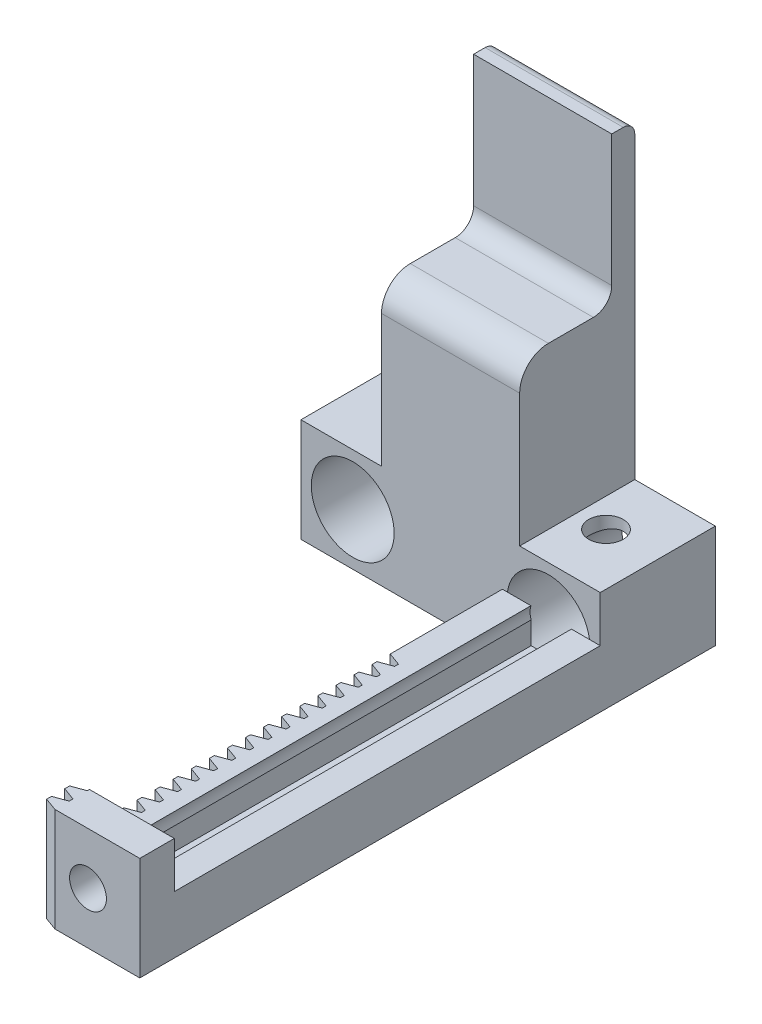
SolidWorks part; units mm, degrees
ref_plane "前视基准面" through (0, 0, 0) normal (0, 0, 1) x (1, 0, 0)
ref_plane "上视基准面" through (0, 0, 0) normal (0, 1, 0) x (1, 0, 0)
ref_plane "右视基准面" through (0, 0, 0) normal (1, 0, 0) x (0, 0, -1)
other "Configuration Table"
sketch "草图1" plane through (0, 0, 0) normal (0, 0, 1) x (1, 0, 0)
  line L1 (-13, 4.5) -> (13, 4.5)
  line L2 (-13, 4.5) -> (-13, -4.5)
  line L3 (-13, -4.5) -> (13, -4.5)
  line L4 (13, 4.5) -> (13, -4.5)
  line L5 (-13, 4.5) -> (13, -4.5) construction
  line L6 (-13, -4.5) -> (13, 4.5) construction
  point P0 (0, 0)
  dimension "D1" = 26
  dimension "D2" = 9
extrude "凸台-拉伸1" add sketch "草图1" against normal blind 10
sketch "草图2" plane through (0, 0, 0) normal (0, 0, 1) x (1, 0, 0)
  line L0 (0, 8.6502) -> (0, -9.0329) construction
  line L1 (8.5, 8.6502) -> (8.5, -9.0329) construction
  line L5 (-13, 0) -> (13, 0)
  line L6 (-13, 0) -> (13, 0) construction
  circle A0 centre (8.5, 0) radius 3.6
  circle A2 centre (-8.5, 0) radius 3.6
  dimension "D4" = 7.2
  dimension "D1" = 8.5
  dimension "D3" = 4.5
extrude "切除-拉伸1" cut sketch "草图2" against normal through all
sketch "草图5" plane through (-13, 0, 0) normal (-1, 0, 0) x (0, 0, 1)
  line L0 (0, 4.5) -> (-10, 4.5)
  line L1 (-10, 4.5) -> (-10, 8.3014)
  line L2 (-10, 8.3014) -> (-10, 30.5)
  line L3 (-9, 31.5) -> (-8, 31.5)
  line L4 (-8, 31.5) -> (-8, 20.1)
  line L5 (-6.4, 18.5) -> (-2.5, 18.5)
  line L6 (0, 16) -> (0, 4.5)
  line L7 (-10, 4.5) -> (-10, -4.5) construction
  arc A0 (-9, 31.5) -> (-10, 30.5) centre (-9, 30.5) ccw
  arc A1 (-6.4, 18.5) -> (-8, 20.1) centre (-6.4, 20.1) cw
  arc A2 (0, 16) -> (-2.5, 18.5) centre (-2.5, 16) ccw
  dimension "D4" = 1
  dimension "D5" = 1.6
  dimension "D6" = 2.5
  dimension "D1" = 27
  dimension "D2" = 14
  dimension "D3" = 8
extrude "凸台-拉伸2" add sketch "草图5" against normal through all
extrude "切除-拉伸2" cut sketch "草图5<2>" against normal blind 7
sketch "草图5<2>" plane through (-13, 0, 0) normal (-1, 0, 0) x (0, 0, 1) same geometry as "草图5"
mirror "镜向1" about plane through (0, 0, 0) normal (1, 0, 0) of "切除-拉伸2"
sketch "草图7" plane through (0, 0, 0) normal (0, 0, 1) x (1, 0, 0)
  line L0 (0, -9.5936) -> (0, 36.1115) construction
  line L2 (4.5, -4.5) -> (4.5, 4.5)
  line L3 (13, 4.5) -> (4.5, 4.5)
  line L4 (13, 4.5) -> (13, -4.5)
  line L5 (13, -4.5) -> (4.5, -4.5)
  line L6 (-13, -4.5) -> (13, -4.5) construction
  line L8 (4.5, -9.5936) -> (4.5, 36.1115) construction
  dimension "D1" = 4.5
extrude "凸台-拉伸3" add sketch "草图7" along normal blind 40
sketch "草图8" plane through (0, 0, 40) normal (0, 0, 1) x (1, 0, 0)
  circle A0 centre (8.5, 0) radius 1.6
  dimension "D1" = 3.2
extrude "切除-拉伸3" cut sketch "草图8" against normal blind 40
sketch "草图9" plane through (0, 4.5, 0) normal (0, 1, 0) x (1, 0, 0)
  line L2 (13, -40) -> (4.5, -40) construction
  line L3 (7, 0) -> (10.5, 0)
  line L5 (6, 10) -> (13, 10) construction
  line L6 (7, -37) -> (10.5, -37)
  line L7 (10.5, 10) -> (10.5, -40)
  line L8 (10.5, 0) -> (10.5, -37)
  line L11 (7, -40) -> (7, 0)
  line L12 (7, -37) -> (7, 0)
  dimension "D1" = 3
  dimension "D2" = 10
  dimension "D3" = 2.5
  dimension "D4" = 2.5
extrude "切除-拉伸4" cut sketch "草图9" against normal blind 7
sketch "草图10" plane through (0, 4.5, 0) normal (0, 1, 0) x (1, 0, 0)
  line L8 (5.625, -40) -> (5.625, -40.3304)
  line L9 (5.625, -40.3304) -> (4.5, -40.7399)
  line L10 (4.5, -40.7399) -> (4.5, -39.5905)
  line L11 (4.5, -39.5905) -> (5.625, -40)
  line L12 (5.625, -40.1652) -> (4.5, -40.1652) construction
  line L13 (5, -39.7725) -> (5, -40.5579) construction
  line L16 (4.5, -40) -> (4.5, 0) construction
  line L17 (13, -40) -> (4.5, -40) construction
  dimension "D1" = 0.625
  dimension "D2" = 0.7854
  dimension "D4" = 0.5
  dimension "D3" = 20
extrude "切除-拉伸12" cut sketch "草图10" against normal through all
pattern_linear "阵列(线性)2" count 20 spacing 1.5708 along (0, 0, -1) of "切除-拉伸12"
sketch "草图22" plane through (0, 4.5, 0) normal (0, 1, 0) x (1, 0, 0)
  line L0 (13, 10) -> (13, -40) construction
  line L5 (4.5, 0) -> (13, 0)
  line L6 (4.5, 0) -> (4.5, -37)
  line L11 (4.5, -37) -> (13, -37)
  line L12 (13, -37) -> (5.625, -37)
  line L13 (21.5249, -37) -> (-0.8919, -37) construction
  line L14 (13, 0) -> (13, -37)
  dimension "D1" = 3
extrude "切除-拉伸13" cut sketch "草图22" against normal blind 4
sketch "草图23" plane through (0, 4.5, 0) normal (0, 1, 0) x (1, 0, 0)
  line L2 (0, 24.8411) -> (0, -13.0368) construction
  line L3 (6, 5) -> (13, 5)
  line L4 (3.4062, 5) -> (18.5675, 5) construction
  line L5 (8.5, 24.8411) -> (8.5, -13.0368) construction
  circle A0 centre (8.5, 5) radius 1.5
  circle A1 centre (-8.5, 5) radius 1.5
  dimension "D3" = 3
  dimension "D1" = 5
  dimension "D2" = 8.5
extrude "切除-拉伸14" cut sketch "草图23" against normal blind 4
equation "\"m\"=0.5 '模数'"
equation "\"t\"=pi * \"m\" '周节'"
equation "\"S\"=pi / 2 * \"m\" '齿厚'"
equation "\"c\"=0.25 * \"m\" '径向间隙'"
equation "\"h1\"=\"m\" '齿顶高'"
equation "\"h2\"=1.25 * \"m\" '齿根高'"
equation "\"hg\"=2 * \"m\" '齿工作高度'"
equation "\"h\"=2.25 * \"m\" '齿全高'"
equation "\"D1@草图10\"=\"h2\""
equation "\"D2@草图10\"=\"S\""
equation "\"D4@草图10\"=\"m\""
equation "\"D3@阵列(线性)2\"=Pi*\"m\""
